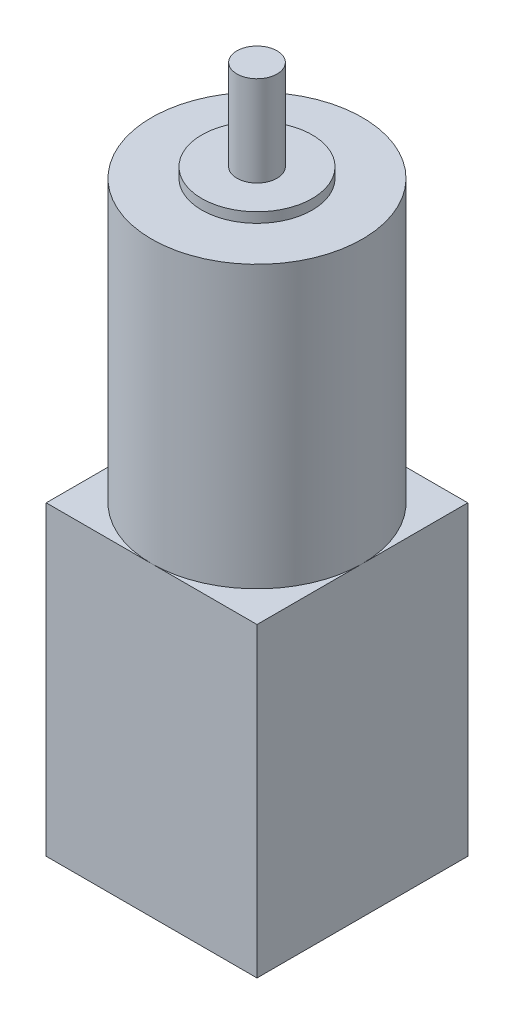
SolidWorks part; units mm, degrees
ref_plane "Front Plane" through (0, 0, 0) normal (0, 0, 1) x (1, 0, 0)
ref_plane "Top Plane" through (0, 0, 0) normal (0, 1, 0) x (1, 0, 0)
ref_plane "Right Plane" through (0, 0, 0) normal (1, 0, 0) x (0, 0, -1)
sketch "Sketch1" plane through (0, 0, 0) normal (0, 1, 0) x (1, 0, 0)
  line L1 (0, 0) -> (42, 0)
  line L2 (0, 0) -> (0, 42)
  line L3 (0, 42) -> (42, 42)
  line L4 (42, 0) -> (42, 42)
  dimension "D1" = 42
extrude "Boss-Extrude1" add sketch "Sketch1" along normal blind 61
sketch "Sketch2" plane through (0, 61, 0) normal (0, 1, 0) x (1, 0, 0)
  line L0 (0, 21) -> (42, 21) construction
  line L1 (0, 42) -> (0, 0) construction
  line L2 (42, 0) -> (42, 42) construction
  line L3 (21, 0) -> (21, 42) construction
  line L4 (0, 0) -> (42, 0) construction
  line L5 (42, 42) -> (0, 42) construction
  circle A0 centre (21, 21) radius 21
  dimension "D1" = 42
extrude "Boss-Extrude2" add sketch "Sketch2" along normal blind 56
sketch "Sketch3" plane through (0, 117, 0) normal (0, 1, 0) x (1, 0, 0)
  line L0 (0, 21) -> (42, 21) construction
  line L1 (21, 0) -> (21, 42) construction
  circle A0 centre (21, 21) radius 21 construction
  circle A1 centre (21, 21) radius 11
  dimension "D1" = 22
extrude "Boss-Extrude3" add sketch "Sketch3" along normal blind 2
sketch "Sketch4" plane through (0, 119, 0) normal (0, 1, 0) x (1, 0, 0)
  line L0 (10, 21) -> (32, 21) construction
  circle A0 centre (21, 21) radius 11 construction
  circle A1 centre (21, 21) radius 11 construction
  circle A2 centre (21, 21) radius 4
  dimension "D1" = 8
extrude "Boss-Extrude4" add sketch "Sketch4" along normal blind 18
